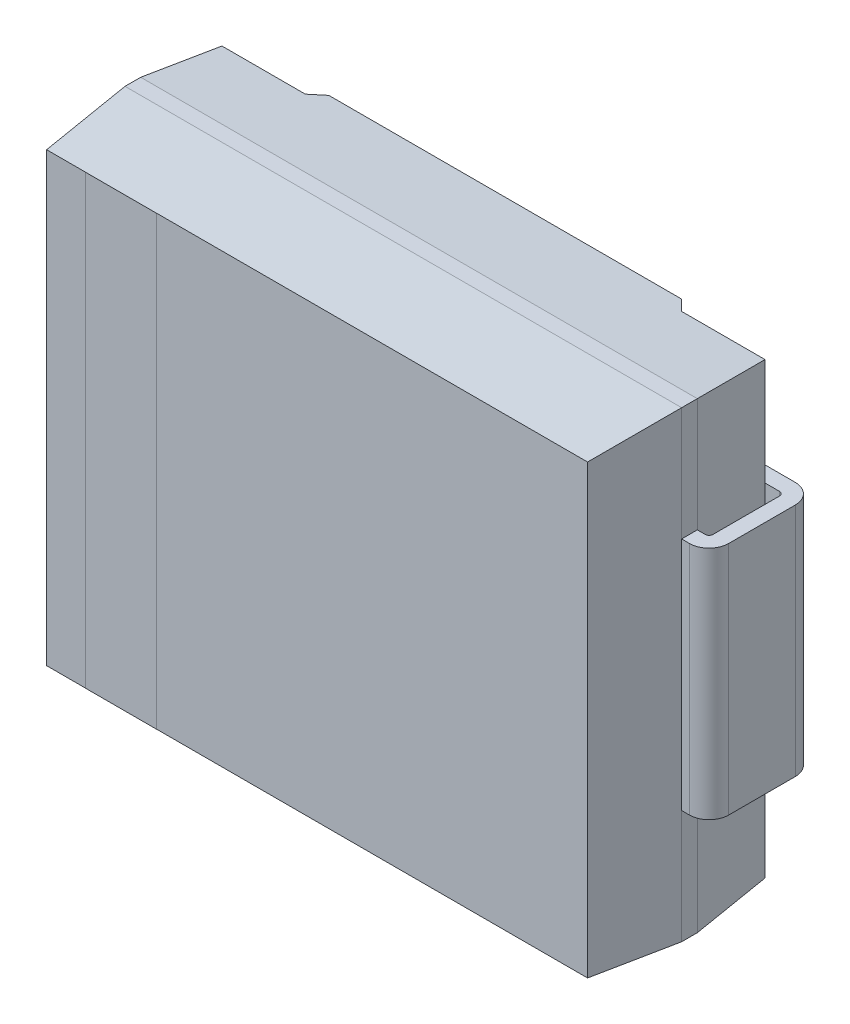
SolidWorks part; units mm, degrees
ref_plane "Płaszczyzna przednia" through (0, 0, 0) normal (0, 0, 1) x (1, 0, 0)
ref_plane "Płaszczyzna górna" through (0, 0, 0) normal (0, 1, 0) x (1, 0, 0)
ref_plane "Płaszczyzna prawa" through (0, 0, 0) normal (1, 0, 0) x (0, 0, -1)
sketch "Szkic1" plane through (0, 0, 0) normal (0, 0, 1) x (1, 0, 0)
  line L1 (3.55, -2.95) -> (-3.55, -2.95)
  line L2 (3.55, -2.95) -> (3.55, 2.95)
  line L3 (3.55, 2.95) -> (-3.55, 2.95)
  line L4 (-3.55, -2.95) -> (-3.55, 2.95)
  line L5 (3.55, -2.95) -> (-3.55, 2.95) construction
  line L6 (3.55, 2.95) -> (-3.55, -2.95) construction
  point P0 (0, 0)
  dimension "D1" = 7.1
  dimension "D2" = 5.9
extrude "Dodanie-wyciągnięcie1" add sketch "Szkic1" along normal blind 2.4
chamfer "Sfazowanie1" distance 1.1 distance2 0.1 4 edges at (0, -2.95, 2.4) (3.55, 0, 2.4) (0, 2.95, 2.4) (-3.55, 0, 2.4) first distance on face at (0, -2.95, 1.2) first distance on face at (3.55, 0, 1.2) first distance on face at (0, 2.95, 1.2) first distance on face at (-3.55, 0, 1.2)
chamfer "Sfazowanie2" distance 0.1 distance2 1.1 4 edges at (0, 2.95, 0) (3.55, 0, 0) (0, -2.95, 0) (-3.55, 0, 0) first distance on face at (0, 0, 0)
sketch "Szkic2" plane through (0, 0, 2.4) normal (0, 0, 1) x (1, 0, 0)
  line L0 (-2.95, 2.85) -> (-2.95, -2.85)
  line L5 (-2.95, -2.85) -> (-2.05, -2.85)
  line L6 (-2.05, -2.85) -> (-2.05, 2.85)
  line L7 (-2.05, 2.85) -> (-2.95, 2.85)
  line L8 (-3.45, 2.85) -> (-3.45, -2.85) construction
  line L9 (-3.45, -2.85) -> (3.45, -2.85) construction
  dimension "D1" = 0.5
  dimension "D2" = 0.9
  dimension "D3" = 5.7
extrude "Dodanie-wyciągnięcie2" add sketch "Szkic2" along normal blind 0.001
sketch "Szkic3" plane through (-3.55, 0, 0) normal (-1, 0, 0) x (0, 0, 1)
  line L0 (1.1, 2.95) -> (1.1, -2.95) construction
  line L1 (0.15, 2.95) -> (0, 2.95)
  line L2 (0.15, 2.95) -> (0.15, -2.95)
  line L3 (0.15, -2.95) -> (0, -2.95)
  line L4 (0, 2.95) -> (0, -2.95)
  line L5 (1.3, 2.95) -> (1.1, 2.95) construction
  line L6 (1.3, -2.95) -> (1.1, -2.95) construction
  dimension "D1" = 0.15
  dimension "D2" = 0.95
extrude "Wytnij-wyciągnięcie1" cut sketch "Szkic3" against normal blind 1.15
chamfer "Sfazowanie3" distance 0.15 angle 45 1 edges at (-2.4, 0, 0)
sketch "Szkic4" plane through (-3.55, 0, 0) normal (-1, 0, 0) x (0, 0, 1)
  line L0 (1.3, -2.95) -> (1.3, 2.95) construction
  line L1 (1.3, 1.5) -> (1.1, 1.5)
  line L2 (1.3, 1.5) -> (1.3, -1.5)
  line L3 (1.3, -1.5) -> (1.1, -1.5)
  line L4 (1.1, 1.5) -> (1.1, -1.5)
  line L5 (1.1, 2.95) -> (1.1, -2.95) construction
  line L6 (1.3, 2.95) -> (1.1, 2.95) construction
  line L8 (1.3, 0) -> (1.1, 0) construction
  dimension "D1" = 1.45
  dimension "D2" = 3
sketch "Szkic5" plane through (0, 0, 0) normal (0, 1, 0) x (1, 0, 0)
  line L0 (-3.55, -1.3) -> (-3.65, -1.3)
  line L1 (-3.9, -1.05) -> (-3.9, -0.2)
  line L2 (-3.65, 0.05) -> (-2.7, 0.05)
  arc A0 (-3.9, -0.2) -> (-3.65, 0.05) centre (-3.65, -0.2) cw
  arc A1 (-3.65, -1.3) -> (-3.9, -1.05) centre (-3.65, -1.05) cw
  point P7 (-3.9, 0.05)
  point P10 (-3.9, -1.3)
  dimension "D4" = 0.25
  dimension "D1" = 0.35
  dimension "D2" = 1.35
  dimension "D3" = 1.2
sweep "Wyciągnięcie po ścieżce1" add profiles "Szkic4" path "Szkic5"
mirror "Lustro1" about plane through (0, 0, 0) normal (1, 0, 0) of "Wyciągnięcie po ścieżce1", "Sfazowanie3", "Wytnij-wyciągnięcie1"
